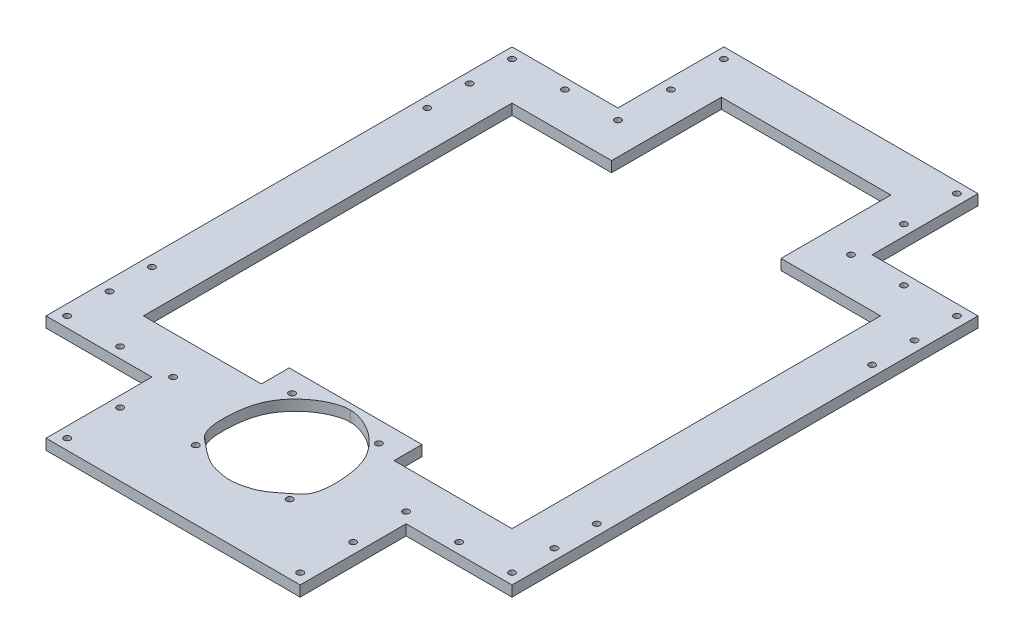
SolidWorks part; units mm, degrees
ref_plane "Plan de face" through (0, 0, 0) normal (0, 0, 1) x (1, 0, 0)
ref_plane "Plan de dessus" through (0, 0, 0) normal (0, 1, 0) x (1, 0, 0)
ref_plane "Plan de droite" through (0, 0, 0) normal (1, 0, 0) x (0, 0, -1)
sketch "Esquisse1" plane through (0, 0, 0) normal (0, 1, 0) x (1, 0, 0)
  line L0 (-60, 110) -> (-60, 160)
  line L1 (110, -110) -> (60, -110)
  line L2 (110, -110) -> (110, 110)
  line L3 (110, 110) -> (60, 110)
  line L4 (-110, -110) -> (-110, 0)
  line L5 (110, -110) -> (-110, 110) construction
  line L6 (110, 110) -> (-110, -110) construction
  line L7 (-60, 160) -> (60, 160)
  line L8 (60, 160) -> (60, 110)
  line L9 (0, 160) -> (0, -160) construction
  line L10 (-110, 0) -> (110, 0) construction
  line L11 (-105, -105) -> (-105, -60) construction
  line L12 (-55, -105) -> (-55, -160) construction
  line L13 (-60, 110) -> (-110, 110)
  line L14 (60, -160) -> (60, -110)
  line L15 (-60, -160) -> (60, -160)
  line L16 (-60, -110) -> (-60, -160)
  line L17 (-60, -110) -> (-110, -110)
  line L23 (-40, 138.8364) -> (40, 138.8364)
  line L28 (-110, 0) -> (-110, 110)
  line L33 (-105, -105) -> (105, -105) construction
  line L34 (105, -105) -> (105, 0) construction
  line L35 (87, -87) -> (31.3269, -87)
  line L36 (87, -87) -> (87, 87)
  line L37 (87, 87) -> (40, 87)
  line L38 (-87, -87) -> (-87, 87)
  line L39 (87, -87) -> (-87, 87) construction
  line L40 (87, 87) -> (-87, -87) construction
  line L41 (40, 138.8364) -> (40, 87)
  line L42 (-40, 138.8364) -> (-40, 87)
  line L46 (-40, 87) -> (-87, 87)
  line L48 (-20.2639, -83.5808) -> (20.6869, -83.5808) construction
  line L49 (0.2938, -104.662) -> (0.2938, -133.662) construction
  line L50 (20.6869, -83.5808) -> (22.477, -127.41) construction
  line L51 (22.477, -127.41) -> (-21.8046, -127.506) construction
  line L52 (-21.8046, -127.506) -> (-20.2639, -83.5808) construction
  line L53 (-20.2639, -83.5808) -> (22.477, -127.41) construction
  line L54 (-21.8046, -127.506) -> (20.6869, -83.5808) construction
  line L55 (-31.3269, -87) -> (-87, -87)
  line L57 (31.3269, -87) -> (31.3269, -73.8394)
  line L58 (31.3269, -73.8394) -> (-31.3269, -73.8394)
  line L59 (-31.3269, -87) -> (-31.3269, -73.8394)
  line L60 (0, -87) -> (-31.3269, -73.8394) construction
  line L61 (31.3269, -73.8394) -> (0, -87) construction
  line L62 (-105, 105) -> (-105, -60) construction
  circle A0 centre (-105, -105) radius 1.5
  circle A1 centre (-105, -65) radius 1.5
  circle A2 centre (-55, -105) radius 1.5
  circle A5 centre (-5, -105) radius 1.5 [skipped]
  circle A6 centre (45, -105) radius 1.5 [skipped]
  circle A7 centre (-55, -155) radius 1.5
  circle A8 centre (-55, 155) radius 1.5
  circle A9 centre (-55, 105) radius 1.5
  circle A10 centre (-105, 105) radius 1.5
  circle A11 centre (-105, 65) radius 1.5
  circle A12 centre (55, -155) radius 1.5
  circle A13 centre (55, -105) radius 1.5
  circle A14 centre (105, -105) radius 1.5
  circle A15 centre (105, 105) radius 1.5
  circle A16 centre (55, 105) radius 1.5
  circle A17 centre (55, 155) radius 1.5
  circle A18 centre (-20.2639, -83.5808) radius 1.5
  circle A19 centre (20.6869, -83.5808) radius 1.5
  circle A20 centre (22.477, -127.41) radius 1.5
  circle A21 centre (-21.8046, -127.506) radius 1.5
  circle A22 centre (105, -65) radius 1.5
  circle A23 centre (105, 65) radius 1.5
  spline S0 degree 3 poles (0.2938, -76.7263) (-0.9961, -76.5783) (-4.6992, -77.2074) (-11.369, -80.0208) (-17.3381, -84.8957) (-23.6991, -93.0991) (-26.4738, -103.394) (-26.3988, -120.1644) (-18.9208, -125.4305) (-12.7349, -130.8054) (-5.3206, -133.1674) (-1.1322, -133.8105) (0.2938, -133.662) knots 0 0 0 0 0.044372 0.129133 0.24756 0.307902 0.482602 0.644889 0.731533 0.853727 0.90962 1 1 1 1
  spline S1 degree 3 poles (0.2938, -76.7263) (1.5836, -76.5783) (5.2868, -77.2074) (11.9565, -80.0208) (17.9257, -84.8957) (24.2867, -93.0991) (27.0614, -103.394) (26.9864, -120.1644) (19.5084, -125.4305) (13.3225, -130.8054) (5.9082, -133.1674) (1.7198, -133.8105) (0.2938, -133.662) knots 0 0 0 0 0.044372 0.129133 0.24756 0.307902 0.482602 0.644889 0.731533 0.853727 0.90962 1 1 1 1
  point P0 (0, 0)
  point P23 (0, 0)
  point P24 (0, 0)
  point P32 (0, 138.8364)
  point P33 (0, 0)
  point P36 (0, -105)
  point P68 (-21.8046, -127.506)
  point P70 (22.477, -127.41)
  point P71 (20.6869, -83.5808)
  point P72 (-20.2639, -83.5808)
  point P77 (0.2938, -104.662)
  dimension "D4" = 3
  dimension "D6" = 50
  dimension "D16" = 5
  dimension "D10" = 21.1636
  dimension "D11" = 29
  dimension "D12" = 40.9508
  dimension "D8" = 23
  dimension "D1" = 220
  dimension "D2" = 50
  dimension "D3" = 50
  dimension "D5" = 5
  dimension "D7" = 120
  dimension "D9" = 20
  dimension "D13" = 2
  dimension "D18" = 44.2816
  dimension "D19" = 92.009
  dimension "D20" = 92.339
  dimension "D21" = 87.867
  dimension "D22" = 40
  dimension "D15" = 4
  dimension "D17" = 2
extrude "Boss.-Extru.1" add sketch "Esquisse1" along normal blind 5
sketch "Esquisse2" plane through (0, 5, 0) normal (0, 1, 0) x (1, 0, 0)
  line L0 (-105, -65) -> (-105, -105) construction
  line L1 (-105, -105) -> (-55, -105) construction
  line L2 (-55, -105) -> (-55, -155) construction
  line L3 (0, -160) -> (0, 160) construction
  line L4 (-60, -160) -> (60, -160) construction
  line L5 (60, 160) -> (-60, 160) construction
  line L6 (-110, 0) -> (110, 0) construction
  line L7 (-110, 110) -> (-110, -110) construction
  line L8 (110, -110) -> (110, 110) construction
  circle A0 centre (-105, -85) radius 1.5
  circle A1 centre (-80, -105) radius 1.5
  circle A2 centre (-55, -130) radius 1.5
  circle A3 centre (55, -130) radius 1.5
  circle A4 centre (80, -105) radius 1.5
  circle A5 centre (105, -85) radius 1.5
  circle A6 centre (105, 85) radius 1.5
  circle A7 centre (80, 105) radius 1.5
  circle A8 centre (55, 130) radius 1.5
  circle A9 centre (-55, 130) radius 1.5
  circle A10 centre (-80, 105) radius 1.5
  circle A11 centre (-105, 85) radius 1.5
  dimension "D1" = 3
extrude "Enlèv. mat.-Extru.1" cut sketch "Esquisse2" against normal up to surface (5 mm away) up to face at (-21.8046, 0, 129.006)
